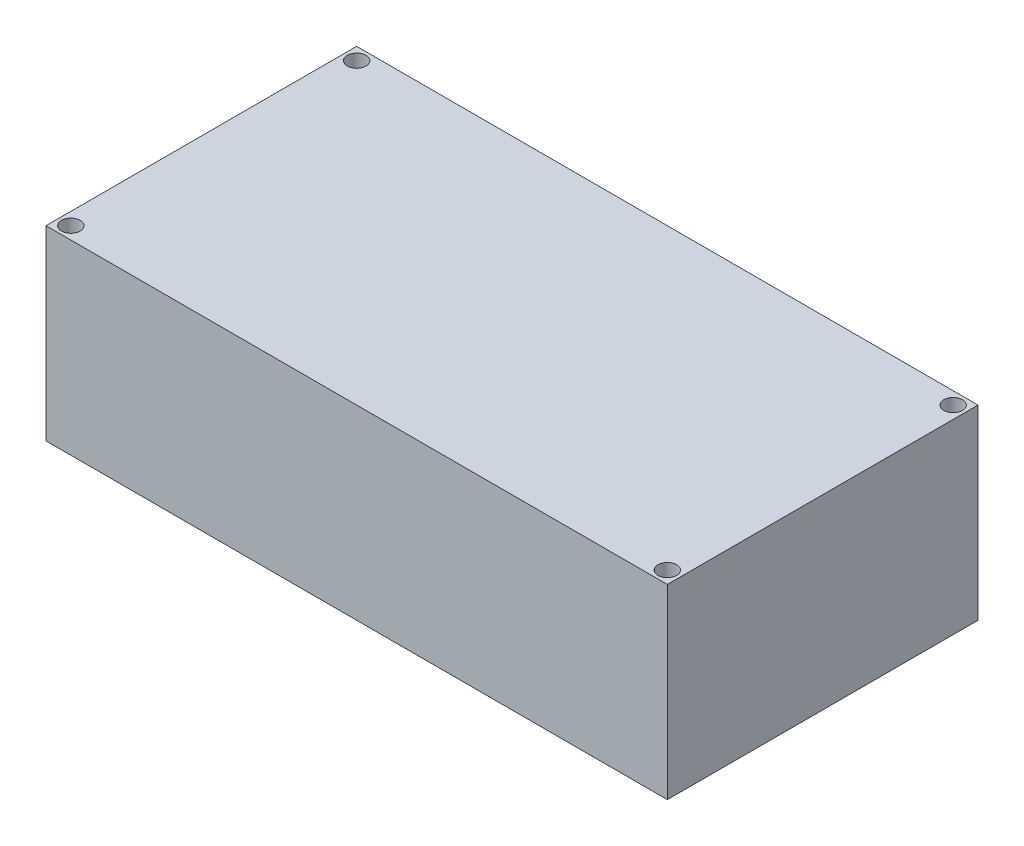
SolidWorks part; units mm, degrees
ref_plane "Plan de face" through (0, 0, 0) normal (0, 0, 1) x (1, 0, 0)
ref_plane "Plan de dessus" through (0, 0, 0) normal (0, 1, 0) x (1, 0, 0)
ref_plane "Plan de droite" through (0, 0, 0) normal (1, 0, 0) x (0, 0, -1)
sketch "Esquisse2" plane through (0, 0, 0) normal (0, 1, 0) x (1, 0, 0)
  line L1 (-50, 25) -> (50, 25)
  line L2 (-50, 25) -> (-50, -25)
  line L3 (-50, -25) -> (50, -25)
  line L4 (50, 25) -> (50, -25)
  dimension "D1" = 100
  dimension "D2" = 50
  dimension "D3" = 50
  dimension "D4" = 25
extrude "Boss.-Extru.1" add sketch "Esquisse2" along normal blind 30
sketch "Esquisse3" plane through (0, 30, 0) normal (0, 1, 0) x (1, 0, 0)
  line L0 (-50, 25) -> (-50, -25) construction
  line L1 (-48, 23) -> (48, 23) construction
  line L2 (-48, 23) -> (-48, -23) construction
  line L3 (-48, -23) -> (48, -23) construction
  line L4 (48, 23) -> (48, -23) construction
  line L5 (50, 25) -> (-50, 25) construction
  line L7 (-50, -25) -> (50, -25) construction
  line L8 (0, 38.0881) -> (0, -39.8087) construction
  circle A0 centre (-48, 23) radius 1.5
  circle A1 centre (-48, -23) radius 1.5
  circle A2 centre (48, -23) radius 1.5
  circle A3 centre (48, 23) radius 1.5
  dimension "D5" = 3
  dimension "D6" = 3
  dimension "D1" = 2
  dimension "D2" = 2
  dimension "D4" = 2
extrude "Enlèv. mat.-Extru.1" cut sketch "Esquisse3" against normal blind 30
equation "\"D3@Esquisse2\"=\"D1@Esquisse2\"/2"
equation "\"D4@Esquisse2\"=\"D2@Esquisse2\"/2"
